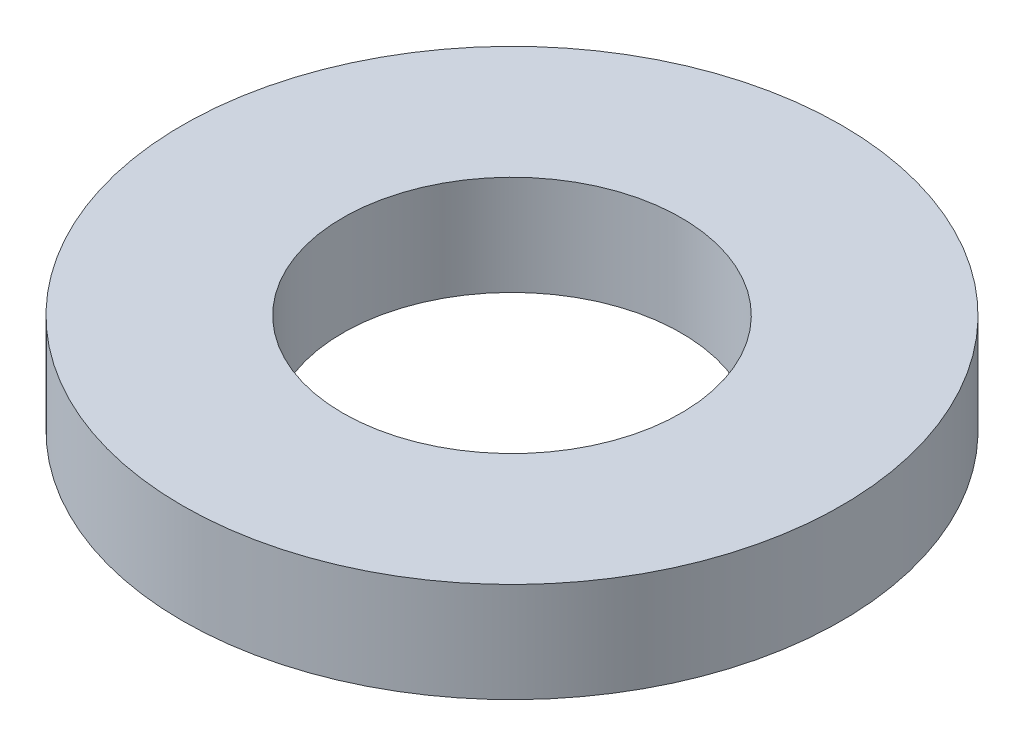
SolidWorks part; units mm, degrees
ref_plane "Front Plane" through (0, 0, 0) normal (0, 0, 1) x (1, 0, 0)
ref_plane "Top Plane" through (0, 0, 0) normal (0, 1, 0) x (1, 0, 0)
ref_plane "Right Plane" through (0, 0, 0) normal (1, 0, 0) x (0, 0, -1)
sketch "Sketch1" plane through (0, 0, 0) normal (0, 1, 0) x (1, 0, 0)
  circle A0 centre (0, 0) radius 92.5
  dimension "FLANGE_OD" = 185
extrude "Boss-Extrude1" add sketch "Sketch1" along normal blind 28
sketch "Sketch2" plane through (0, 0, 0) normal (0, 1, 0) x (1, 0, 0)
  circle A0 centre (0, 0) radius 47.5
  dimension "BORE_D" = 95
extrude "Cut-Extrude1" cut sketch "Sketch2" along normal through all
sketch "Sketch3" plane through (0, 28, 0) normal (0, 1, 0) x (1, 0, 0)
  circle A0 centre (0, 0) radius 27.9211 construction
  circle A1 centre (-27.9211, 0) radius 3.1197
  dimension "BOLT_D" = 6.2394
  dimension "BOLT_PCD" = 55.8422
extrude "Cut-Extrude2" cut sketch "Sketch3" against normal blind 23.281 rebuild error yes
pattern_circular "CirPattern1" count 5 over 360 rebuild error yes
